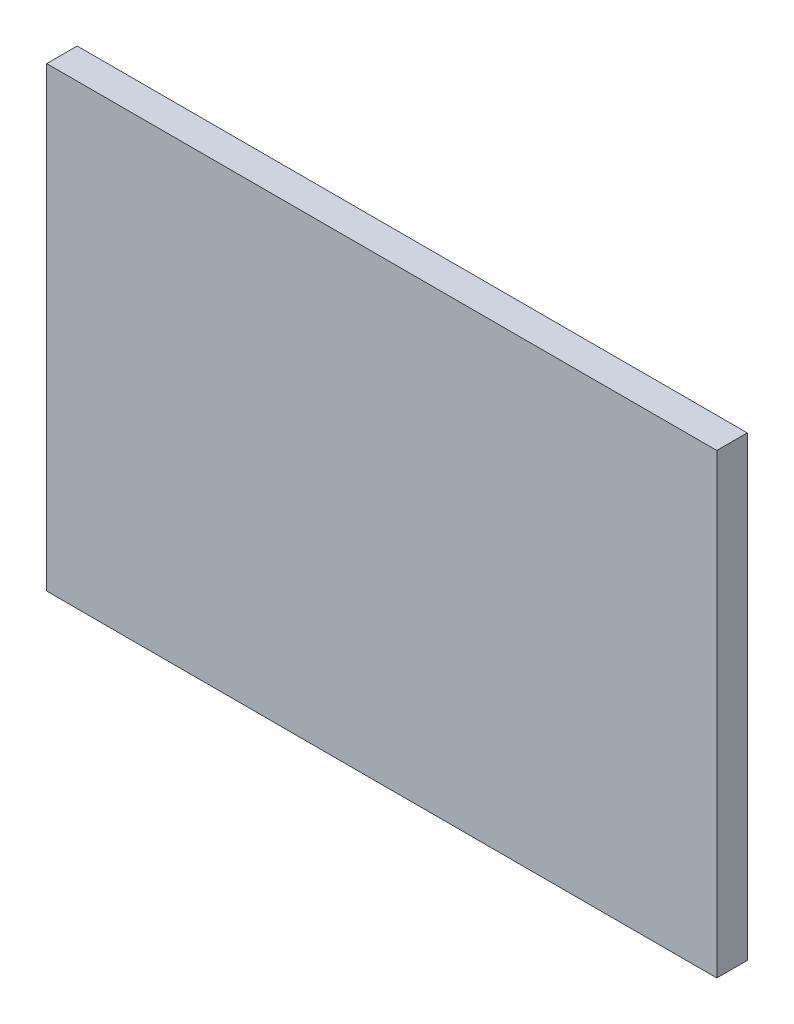
SolidWorks part; units mm, degrees
material "Nickel"
ref_plane "Plane1" through (0, 0, 0) normal (0, 0, 1) x (1, 0, 0)
ref_plane "Plane2" through (0, 0, 0) normal (0, 1, 0) x (1, 0, 0)
ref_plane "Plane3" through (0, 0, 0) normal (1, 0, 0) x (0, 0, -1)
sketch "Sketch1" plane through (0, 0, 0) normal (0, 0, 1) x (1, 0, 0)
  line L0 (-11, -0.0588) -> (11, -0.0588)
  line L1 (0, -10) -> (0, 14.9412) construction
  line L3 (11, 14.9412) -> (11, -0.0588)
  line L4 (11, 14.9412) -> (-11, 14.9412)
  line L5 (-11, 14.9412) -> (-11, -0.0588)
  dimension "D3" = 11
  dimension "D4" = 15
extrude "Extrude1" add sketch "Sketch1" along normal blind 1
sketch "Sketch2" plane through (11, 0, 0) normal (1, 0, 0) x (0, 0, -1)
  line L0 (-1, 14.9412) -> (-7.6228, 14.9412) construction
  circle A0 centre (-4.5, 14.9412) radius 4.5
  circle A1 centre (-4.5, 14.9412) radius 3.5
  dimension "D1" = 7
ref_axis "Clip Axis" through (-10.8102, 14.9412, 4.5) along (1, 0, 0)
sketch "Sketch5" plane through (-11, 0, 0) normal (-1, 0, 0) x (0, 0, 1)
  point P0 (4.5, 14.9412)
sketch "FilterSketch" plane through (11, 0, 0) normal (1, 0, 0) x (0, 0, -1)
  circle A0 centre (-4.5, 14.9412) radius 3 construction
  circle A1 centre (-4.5, 14.9412) radius 0.05 construction
  circle A2 centre (-4.5, 14.9412) radius 3.25 construction
  dimension "NominalDiameter" = 6
  dimension "InnerDiameter" = 0.1
  dimension "OuterDiameter" = 6.5
other "RPoint1"
ref_axis "Axis4" through (16, 14.9412, 4.5) along (-1, 0, 0)
ref_axis "Axis of Rotation" through (-11, 14.9412, 1) along (1, 0, 0)
